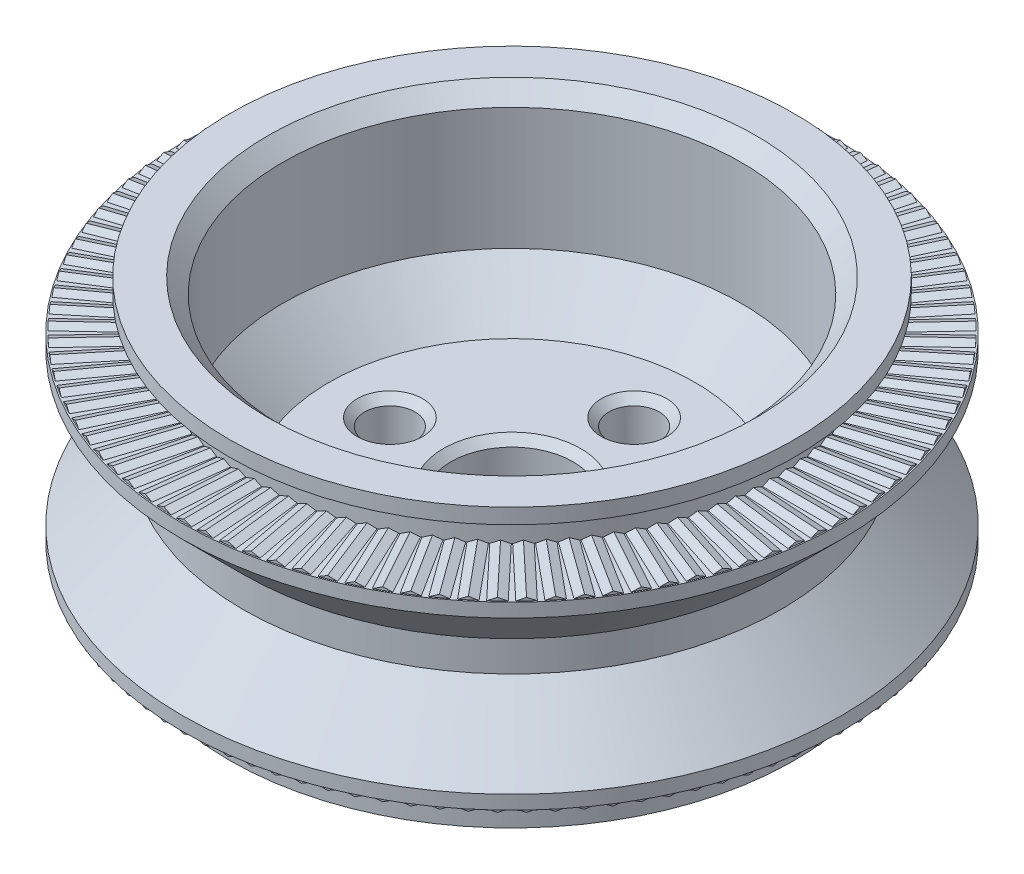
SolidWorks part; units mm, degrees
ref_plane "前视基准面" through (0, 0, 0) normal (0, 0, 1) x (1, 0, 0)
ref_plane "上视基准面" through (0, 0, 0) normal (0, 1, 0) x (1, 0, 0)
ref_plane "右视基准面" through (0, 0, 0) normal (1, 0, 0) x (0, 0, -1)
other "Configuration Table"
sketch "草图1" plane through (0, 0, 0) normal (0, 1, 0) x (1, 0, 0)
  circle A0 centre (0, 0) radius 21.6
  dimension "D1" = 43.2
extrude "凸台-拉伸1" add sketch "草图1" along normal mid plane 18.2
sketch "草图2" plane through (0, 0, 0) normal (0, 0, 1) x (1, 0, 0)
  line L0 (21.6, -9.1) -> (21.6, 9.1) construction
  line L1 (21.6, -8.1) -> (16.9, -8.1)
  line L2 (21.6, -8.1) -> (21.6, -5.9)
  line L3 (21.6, -5.9) -> (16.9, -5.9)
  line L4 (16.9, -8.1) -> (16.9, -5.9)
  line L5 (-21.6, -9.1) -> (21.6, -9.1) construction
  line L6 (18.5, -9.1) -> (21.6, -9.1)
  line L7 (18.5, -9.1) -> (18.5, -8.1)
  line L8 (18.5, -8.1) -> (21.6, -8.1)
  line L9 (21.6, -9.1) -> (21.6, -8.1)
  dimension "D1" = 4.7
  dimension "D2" = 18.5
  dimension "D3" = 3.2
  dimension "D4" = 1
ref_axis "基准轴1" through (0, 9.1, 0) along (0, -1, 0)
revolve "切除-旋转1" cut sketch "草图2" angle 360 about axis through (0, 9.1, 0) along (0, -1, 0) region at (20.05, -8.6, 0) region at (19.25, -7, 0)
mirror "镜向1" about plane through (0, 0, 0) normal (0, 1, 0) of "切除-旋转1"
sketch "草图3" plane through (0, -9.1, 0) normal (0, -1, 0) x (1, 0, 0)
  circle A0 centre (0, 0) radius 15
  dimension "D1" = 30
extrude "切除-拉伸1" cut sketch "草图3" against normal blind 3
sketch "草图4" plane through (0, -6.1, 0) normal (0, -1, 0) x (1, 0, 0)
  circle A0 centre (0, 0) radius 4
  dimension "D1" = 8
extrude "切除-拉伸2" cut sketch "草图4" against normal blind 20
sketch "草图5" plane through (0, -6.1, 0) normal (0, -1, 0) x (1, 0, 0)
  circle A0 centre (-8, 0) radius 1.65
  dimension "D2" = 3.3
  dimension "D1" = 8
extrude "切除-拉伸3" cut sketch "草图5" against normal blind 20
pattern_circular "阵列(圆周)1" count 4 over 360 about axis through (0, 9.1, 0) along (0, -1, 0) of "切除-拉伸3"
extrude "切除-拉伸4" cut sketch "草图3<2>" along normal blind 12 from surface starting at face at (0, 9.1, -6.35)
sketch "草图3<2>" plane through (0, -9.1, 0) normal (0, -1, 0) x (1, 0, 0) same geometry as "草图3"
sketch "草图6" plane through (0, 0, 0) normal (0, 0, 1) x (1, 0, 0)
  line L5 (21.6, -5.9) -> (21.6, 5.9) construction
  line L6 (17.6, -5) -> (21.6, -5)
  line L7 (17.6, -5) -> (17.6, 5)
  line L8 (17.6, 5) -> (21.6, 5)
  line L9 (21.6, -5) -> (21.6, 5)
  line L10 (17.6, -5) -> (21.6, 5) construction
  line L11 (17.6, 5) -> (21.6, -5) construction
  point P0 (19.6, 0)
  dimension "D1" = 4
  dimension "D2" = 10
revolve "切除-旋转2" cut sketch "草图6" angle 360 about axis through (0, 9.1, 0) along (0, -1, 0)
chamfer "倒角1" distance 4 angle 45 2 edges at (0, -5, 17.6) (0, 5, 17.6)
chamfer "倒角2" distance 3 angle 45 2 edges at (0, -6.1, -15) (0, -2.9, 15)
chamfer "倒角3" distance 1 angle 45 1 edges at (0, 9.1, 15)
chamfer "倒角4" distance 0.5 angle 45 10 edges at (0, -2.9, -6.35) (1.65, -6.1, -8) (-8, -2.9, 1.65) (-8, -6.1, -1.65) (8, -2.9, 1.65) (8, -6.1, 1.65) (0, -2.9, 4) (0, -6.1, -4) (0, -2.9, 9.65) (-1.65, -6.1, 8)
sketch "草图7" plane through (0, 0, 0) normal (0, 0, 1) x (1, 0, 0)
  line L0 (-0.5, 5.9) -> (0, 6.1)
  line L1 (21.6, 5.9) -> (-21.6, 5.9) construction
  line L2 (0, 6.1) -> (0.5, 5.9)
  line L3 (0.5, 5.9) -> (-0.5, 5.9)
  point P4 (0, 0)
  dimension "D1" = 1
  dimension "D2" = 0.2
extrude "凸台-拉伸4" add sketch "草图7" along normal blind 5.5 from offset 16
pattern_circular "阵列(圆周)2" count 100 over 360 about axis through (0, 9.1, 0) along (0, -1, 0) of "凸台-拉伸4"
mirror "镜向2" about plane through (0, 0, 0) normal (0, 1, 0) of "阵列(圆周)2"
